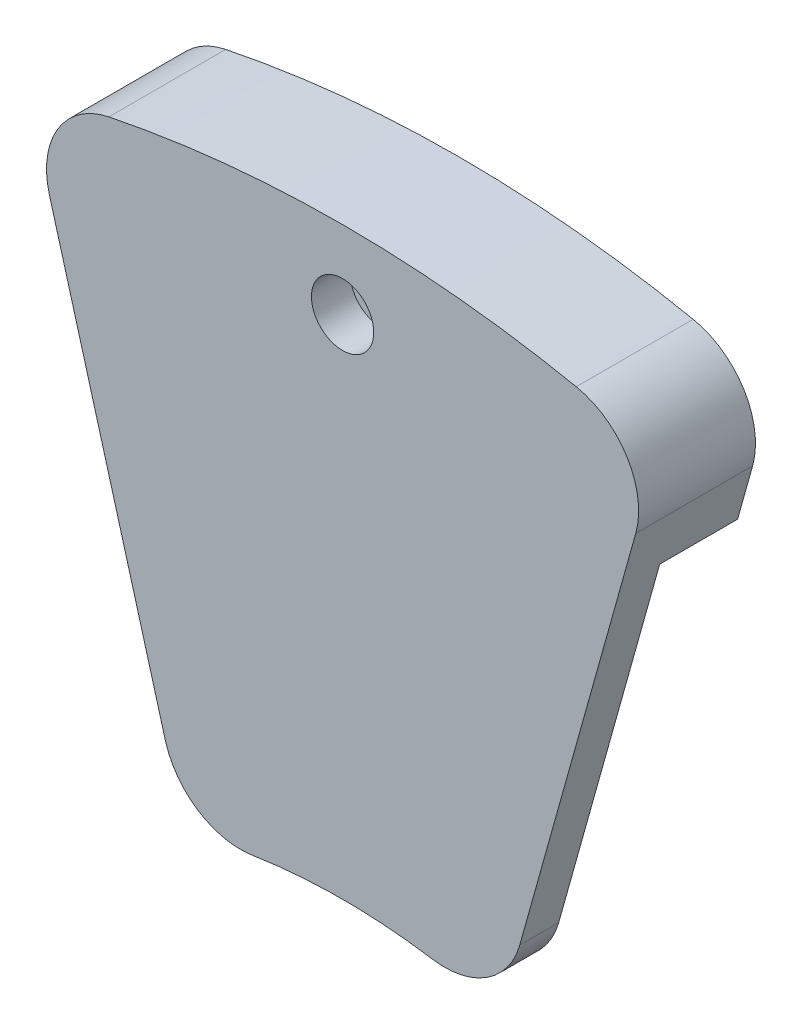
SolidWorks part; units mm, degrees
ref_plane "前视基准面" through (0, 0, 0) normal (0, 0, 1) x (1, 0, 0)
ref_plane "上视基准面" through (0, 0, 0) normal (0, 1, 0) x (1, 0, 0)
ref_plane "右视基准面" through (0, 0, 0) normal (1, 0, 0) x (0, 0, -1)
sketch "草图1" plane through (0, 0, 0) normal (0, 0, 1) x (1, 0, 0)
  line L2 (-37.6301, 134.4767) -> (-22.7463, 81.2872)
  line L3 (22.7463, 81.2872) -> (37.6301, 134.4767)
  line L4 (-37.6301, 134.4767) -> (-22.7463, 81.2872)
  line L5 (22.7463, 81.2872) -> (37.6301, 134.4767)
  arc A0 (0, 136) -> (0, 144) centre (0, 140) ccw construction
  arc A1 (0, 144) -> (0, 136) centre (0, 140) ccw construction
  arc A2 (0, 144) -> (0, 136) centre (0, 140) ccw
  arc A3 (0, 136) -> (0, 144) centre (0, 140) ccw
  arc A8 (-22.7463, 81.2872) -> (-13.1162, 73.9819) centre (-13.1162, 83.9819) ccw
  arc A9 (-13.1162, 73.9819) -> (-11.5731, 74.1017) centre (-13.1162, 83.9819) ccw
  arc A10 (11.5731, 74.1017) -> (-11.5731, 74.1017) centre (0, 0) ccw
  arc A11 (11.5731, 74.1017) -> (13.1162, 73.9819) centre (13.1162, 83.9819) ccw
  arc A12 (13.1162, 73.9819) -> (22.7463, 81.2872) centre (13.1162, 83.9819) ccw
  arc A13 (37.6301, 134.4767) -> (30, 146.9694) centre (28, 137.1714) ccw
  arc A14 (30, 146.9694) -> (-30, 146.9694) centre (0, 0) ccw
  arc A15 (-30, 146.9694) -> (-37.6301, 134.4767) centre (-28, 137.1714) ccw
  arc A16 (-22.7463, 81.2872) -> (-13.1162, 73.9819) centre (-13.1162, 83.9819) ccw
  arc A17 (-13.1162, 73.9819) -> (-11.5731, 74.1017) centre (-13.1162, 83.9819) ccw
  arc A18 (11.5731, 74.1017) -> (-11.5731, 74.1017) centre (0, 0) ccw
  arc A19 (11.5731, 74.1017) -> (13.1162, 73.9819) centre (13.1162, 83.9819) ccw
  arc A20 (13.1162, 73.9819) -> (22.7463, 81.2872) centre (13.1162, 83.9819) ccw
  arc A21 (37.6301, 134.4767) -> (30, 146.9694) centre (28, 137.1714) ccw
  arc A22 (30, 146.9694) -> (-30, 146.9694) centre (0, 0) ccw
  arc A23 (-30, 146.9694) -> (-37.6301, 134.4767) centre (-28, 137.1714) ccw
  dimension "D1" = 0
extrude "凸台-拉伸1" add sketch "草图1" along normal blind 5
sketch "草图2" plane through (0, 0, 0) normal (0, 0, -1) x (-1, 0, 0)
  line L0 (37.6301, 134.4767) -> (22.7463, 81.2872) construction
  line L1 (-22.7463, 81.2872) -> (-37.6301, 134.4767) construction
  line L2 (37.6301, 134.4767) -> (35.7054, 127.5985)
  line L3 (-35.7054, 127.5985) -> (-37.6301, 134.4767)
  arc A0 (-30, 146.9694) -> (-37.6301, 134.4767) centre (-28, 137.1714) ccw construction
  arc A1 (30, 146.9694) -> (-30, 146.9694) centre (0, 0) ccw construction
  arc A2 (37.6301, 134.4767) -> (30, 146.9694) centre (28, 137.1714) ccw construction
  arc A3 (-30, 146.9694) -> (-37.6301, 134.4767) centre (-28, 137.1714) ccw
  arc A4 (30, 146.9694) -> (-30, 146.9694) centre (0, 0) ccw
  arc A5 (37.6301, 134.4767) -> (30, 146.9694) centre (28, 137.1714) ccw
  arc A6 (35.7054, 127.5985) -> (-35.7054, 127.5985) centre (0, 0) ccw
  dimension "D1" = 132.5
extrude "凸台-拉伸2" add sketch "草图2" along normal blind 10
